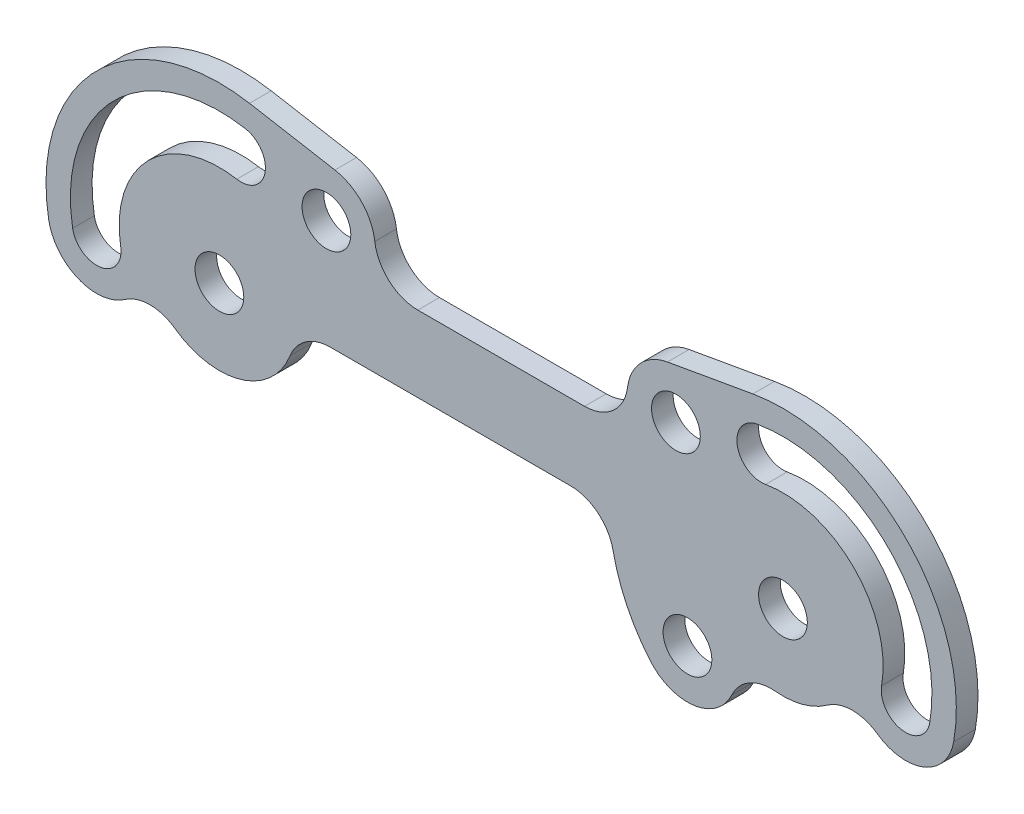
SolidWorks part; units mm, degrees
ref_plane "Front Plane" through (0, 0, 0) normal (0, 0, 1) x (1, 0, 0)
ref_plane "Top Plane" through (0, 0, 0) normal (0, 1, 0) x (1, 0, 0)
ref_plane "Right Plane" through (0, 0, 0) normal (1, 0, 0) x (0, 0, -1)
sketch "Sketch1" plane through (0, 0, 0) normal (0, 0, 1) x (1, 0, 0)
  line L0 (20.6375, 0) -> (-20.6375, 0)
  line L1 (-20.6375, 0) -> (-20.6375, 5.5562) construction
  line L2 (-20.6375, 0) -> (-18.4322, 12.5071) construction
  line L3 (-20.6375, 0) -> (-26.1937, 0) construction
  line L4 (-20.6375, 0) -> (-33.1446, -2.2053) construction
  line L5 (-19.0524, 8.9894) -> (-12.7989, 7.8868) construction
  line L6 (-10.0921, 5.5562) -> (10.0921, 5.5562)
  line L7 (0, 5.5562) -> (0, 0)
  line L8 (-12.1786, 11.4044) -> (-13.4191, 4.3692) construction
  line L9 (-18.4322, 12.5071) -> (-12.1786, 11.4044)
  line L10 (0, 5.5562) -> (0, -5.5619) construction
  line L11 (12.1786, 11.4044) -> (13.4191, 4.3692) construction
  line L12 (19.0524, 8.9894) -> (12.7989, 7.8868) construction
  line L13 (20.6375, 0) -> (33.1446, -2.2053) construction
  line L14 (20.6375, 0) -> (26.1937, 0) construction
  line L15 (20.6375, 0) -> (18.4322, 12.5071) construction
  line L16 (20.6375, 0) -> (20.6375, 5.5562) construction
  line L17 (18.4322, 12.5071) -> (12.1786, 11.4044)
  line L18 (13.645, -5.8674) -> (20.6375, 0) construction
  circle A0 centre (-20.6375, 0) radius 1.7859
  circle A2 centre (-20.6375, 0) radius 9.1281 construction
  circle A3 centre (-20.6375, 0) radius 5.5562
  circle A4 centre (-19.0524, 8.9894) radius 1.7859
  circle A5 centre (-29.6269, -1.5851) radius 1.7859
  circle A7 centre (-12.7989, 7.8868) radius 1.7859
  circle A8 centre (-29.6269, -1.5851) radius 3.5719
  circle A9 centre (-19.0524, 8.9894) radius 3.5719
  circle A10 centre (-12.7989, 7.8868) radius 3.5719
  arc A11 (-19.3625, 7.2306) -> (-27.8681, -1.275) centre (-20.6375, 0) ccw
  arc A12 (-18.7423, 10.7483) -> (-31.3858, -1.8952) centre (-20.6375, 0) ccw
  arc A13 (-18.4322, 12.5071) -> (-33.1446, -2.2053) centre (-20.6375, 0) ccw
  circle A14 centre (20.6375, 0) radius 9.1281 construction
  arc A15 (18.4322, 12.5071) -> (33.1446, -2.2053) centre (20.6375, 0) cw
  arc A16 (18.7423, 10.7483) -> (31.3858, -1.8952) centre (20.6375, 0) cw
  arc A17 (19.3625, 7.2306) -> (27.8681, -1.275) centre (20.6375, 0) cw
  circle A18 centre (12.7989, 7.8868) radius 3.5719
  circle A19 centre (19.0524, 8.9894) radius 3.5719
  circle A20 centre (29.6269, -1.5851) radius 3.5719
  circle A21 centre (12.7989, 7.8868) radius 1.7859
  circle A22 centre (29.6269, -1.5851) radius 1.7859
  circle A23 centre (19.0524, 8.9894) radius 1.7859
  circle A24 centre (20.6375, 0) radius 5.5562
  circle A25 centre (20.6375, 0) radius 1.7859
  circle A26 centre (13.645, -5.8674) radius 3.5719
  circle A27 centre (13.645, -5.8674) radius 1.7859
  arc A28 (10.9087, -8.1634) -> (7.9375, 0) centre (20.6375, 0) cw
  point P59 (7.9375, 0)
  dimension "D1" = 3.5719
  dimension "D5" = 11.1125
  dimension "D6" = 7.1437
  dimension "D2" = 20.6375
  dimension "D3" = 10
  dimension "D4" = 10
  dimension "D7" = 6.35
  dimension "D8" = 40
extrude "Boss-Extrude1" add sketch "Sketch1" along normal blind 1.5875 contours A3 A0 | A12 A8 A11 A5 | A9 A13 A8 A12 | A9 A11 A8 A3 | A12 A4 A11 A9 A10 | A9 A10 | A10 L9 A9 | A10 A9 A7 | A10 A9 A3 L0 L7 L6 | L0 A24 A19 A18 L6 L7 | A18 A19 A21 | A18 A19 L17 | A17 A23 A16 A19 A18 | A19 A18 | A25 A24 | A19 A24 A20 A17 | A16 A20 A15 A19 | A16 A22 A17 A20 | A26 A27 | A28 A26 A24 L0 region at (8.0349, 2.8138, 0) region at (11.1226, -2.0425, 0) region at (-8.0349, 2.8138, 0) region at (16.5016, 3.4705, 0) region at (11.4139, -3.2086, 0) region at (-20.1669, -5.3786, 0) region at (17.7862, 5.753, 0) region at (24.8448, 4.2073, 0) region at (-24.8448, 4.2073, 0) region at (-21.0384, 6.1375, 0) region at (-26.1659, -1.2823, 0) region at (-13.5048, 4.4873, 0) region at (9.5288, 9.0535, 0) region at (15.9257, 8.4381, 0) region at (26.7759, 0.4003, 0) region at (-15.9257, 8.4381, 0) region at (15.3989, 11.4257, 0) region at (32.9141, 0.2866, 0) region at (-28.504, 7.8665, 0) region at (-15.3989, 11.4257, 0)
fillet "Fillet1" radius 3.175 7 edges at (-26.1093, -0.9648, 0.7937) (-15.0813, 0, 0.7937) (-10.0921, 5.5562, 0.7937) (26.1093, -0.9648, 0.7937) (16.3812, -3.5715, 0.7937) (10.0921, 5.5562, 0.7937) (7.9375, 0, 0.7937)
